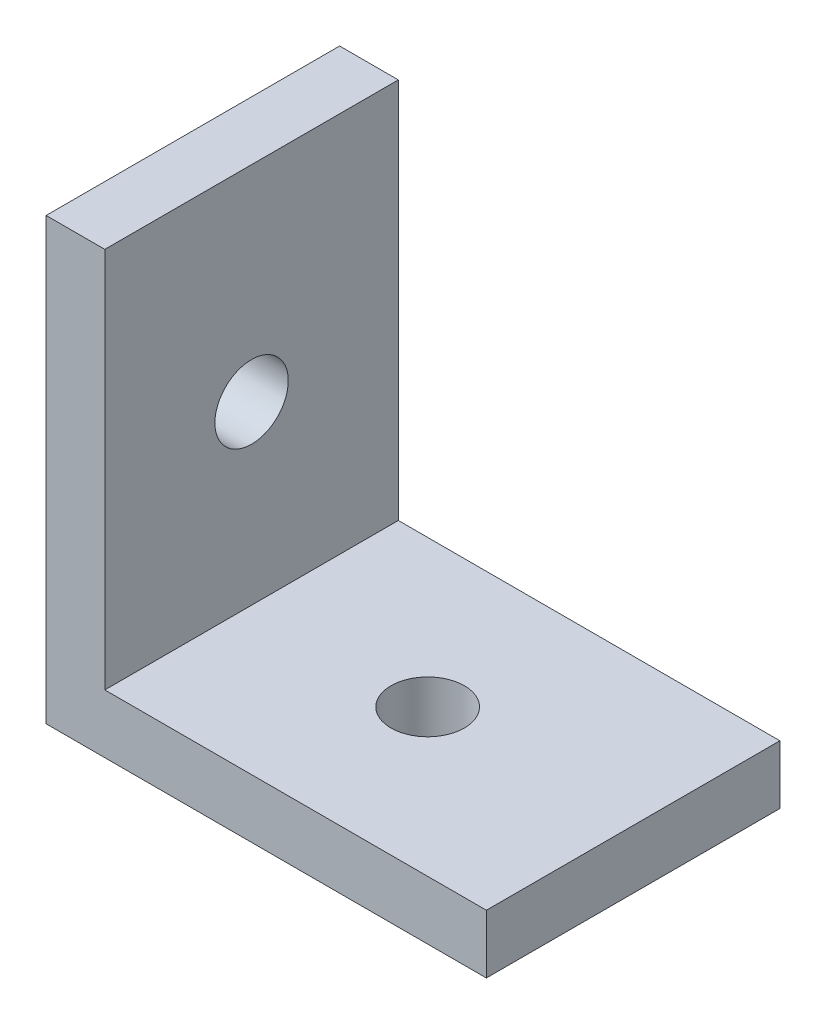
SolidWorks part; units mm, degrees
material "1060 Alloy"
ref_plane "Front Plane" through (0, 0, 0) normal (0, 0, 1) x (1, 0, 0)
ref_plane "Top Plane" through (0, 0, 0) normal (0, 1, 0) x (1, 0, 0)
ref_plane "Right Plane" through (0, 0, 0) normal (1, 0, 0) x (0, 0, -1)
sketch "Sketch1" plane through (0, 0, 0) normal (0, 0, 1) x (1, 0, 0)
  line L0 (0, 0) -> (0, 15)
  line L1 (0, 15) -> (2, 15)
  line L2 (2, 15) -> (2, 2)
  line L3 (2, 2) -> (15, 2)
  line L4 (15, 2) -> (15, 0)
  line L5 (15, 0) -> (0, 0)
  dimension "D1" = 2
  dimension "D2" = 15
extrude "Base" add sketch "Sketch1" along normal mid plane 10
sketch "Sketch2" plane through (0, 0, 0) normal (-1, 0, 0) x (0, 0, 1)
  line L0 (5, 0) -> (-5, 0) construction
  circle A0 centre (0, 8) radius 1.25
  point P4 (0, 0)
  dimension "D1" = 2.5
  dimension "D2" = 8
extrude "Cut-Extrude1" cut sketch "Sketch2" against normal through all
cosmetic thread "Cosmetic Thread1" parameters "D2"=3
sketch "Sketch3" plane through (0, 0, 0) normal (0, -1, 0) x (1, 0, 0)
  line L0 (0, 5) -> (0, -5) construction
  circle A0 centre (8, 0) radius 1.25
  dimension "D1" = 2.5
  dimension "D2" = 8
extrude "Cut-Extrude2" cut sketch "Sketch3" against normal blind 10
cosmetic thread "Cosmetic Thread2" parameters "D2"=3
